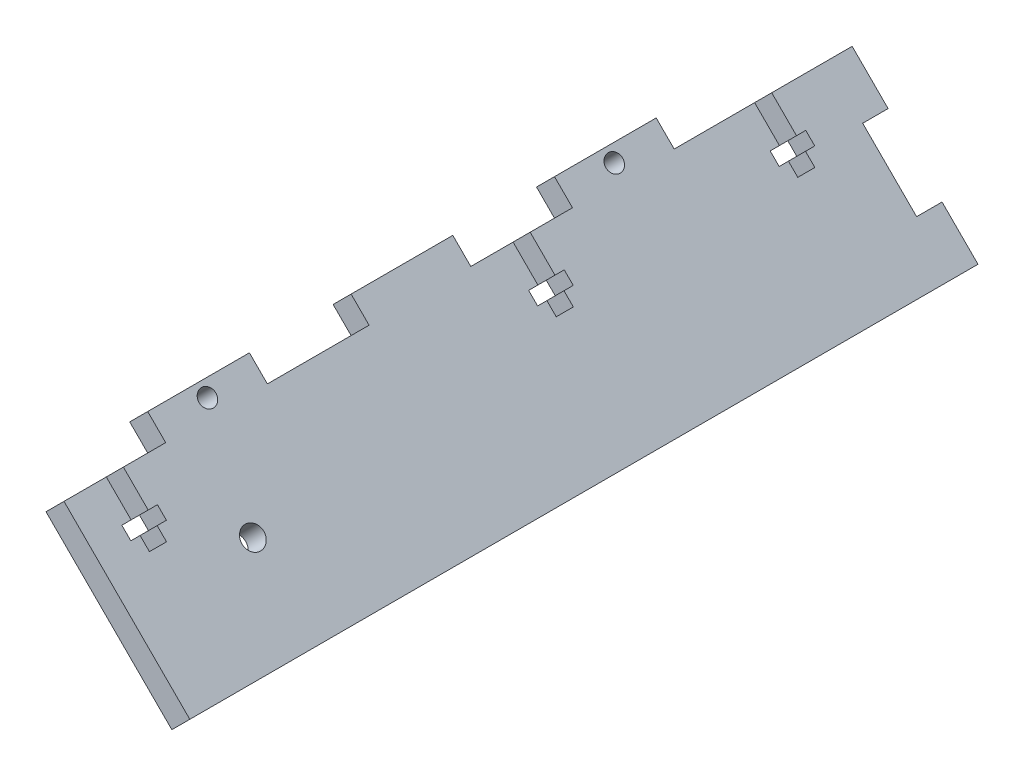
SolidWorks part; units mm, degrees
ref_plane "Front Plane" through (0, 0, 0) normal (0, 0, 1) x (1, 0, 0)
ref_plane "Top Plane" through (0, 0, 0) normal (0, 1, 0) x (1, 0, 0)
ref_plane "Right Plane" through (0, 0, 0) normal (1, 0, 0) x (0, 0, -1)
sketch "Sketch1" plane through (0, 0, 0) normal (0, 0, 1) x (1, 0, 0)
  line L0 (-105.5101, 43.1479) -> (-54.0999, -8.2622) construction
  line L1 (-21.1674, -45.6848) -> (-64.2712, -2.5811) construction
  line L2 (-59.7811, 1.9091) -> (-16.6773, -41.1947) construction
  line L3 (-71.393, 41.3598) -> (-39.9621, 9.9289)
  line L4 (-71.393, 41.3598) -> (-66.9029, 45.85)
  line L5 (-39.9621, 9.9289) -> (-35.472, 14.4191)
  line L6 (-66.9029, 45.85) -> (-35.472, 14.4191)
  line L7 (-72.2911, -22.4) -> (-103.722, 9.0309) construction
  line L8 (-76.7812, -26.8901) -> (-72.2911, -22.4) construction
extrude "Boss-Extrude1" add sketch "Sketch1" along normal up to surface (190.5 mm away)
sketch "Sketch2" plane through (-56.3764, 56.3764, 0) normal (-0.7071, 0.7071, 0) x (0, 0, 1)
  line L0 (190.5, -14.8867) -> (0, -14.8867) construction
  line L1 (165.1, -14.8867) -> (139.7, -14.8867)
  line L2 (165.1, -14.8867) -> (165.1, -21.2367)
  line L3 (165.1, -21.2367) -> (139.7, -21.2367)
  line L4 (139.7, -14.8867) -> (139.7, -21.2367)
  line L5 (190.5, -21.2367) -> (0, -21.2367) construction
  dimension "D1" = 25.4
  dimension "D2" = 25.4
extrude "Boss-Extrude2" add sketch "Sketch2" along normal blind 6.35
pattern_linear "LPattern1" count 3 spacing 50.8 along (0, 0, -1) of "Boss-Extrude2"
sketch "Sketch3" plane through (0, 0, 0) normal (0, 0, -1) x (-1, 0, 0)
  line L0 (71.393, 41.3598) -> (62.4128, 32.3796)
  line L1 (71.393, 41.3598) -> (39.9621, 9.9289) construction
  line L2 (62.4128, 32.3796) -> (57.9227, 36.8697)
  line L3 (35.472, 14.4191) -> (66.9029, 45.85) construction
  line L4 (57.9227, 36.8697) -> (66.9029, 45.85)
  line L5 (66.9029, 45.85) -> (71.393, 41.3598)
  dimension "D1" = 12.7
extrude "Boss-Extrude3" add sketch "Sketch3" along normal blind 6.35
pattern_linear "LPattern2" count 2 spacing 31.75 along (0.7071, -0.7071, 0) of "Boss-Extrude3"
sketch "Sketch4" plane through (-10.5265, -10.5265, 0) normal (0.7071, 0.7071, 0) x (0, 0, -1)
  circle A0 centre (-159.0375, 57.5033) radius 2.7305
extrude "Cut-Extrude1" cut sketch "Sketch4" against normal through all
sketch "Sketch5" plane through (-10.5265, -10.5265, 0) normal (0.7071, 0.7071, 0) x (0, 0, -1)
  line L0 (-177.8, 79.7283) -> (-177.8, 68.4326) construction
  line L1 (-190.5, 79.7283) -> (-165.1, 79.7283) construction
  line L2 (-76.2, 79.7283) -> (-76.2, 62.5112) construction
  line L3 (-88.9, 79.7283) -> (-63.5, 79.7283) construction
  line L4 (-15.875, 79.7283) -> (-15.875, 66.2052) construction
  line L5 (-38.1, 79.7283) -> (6.35, 79.7283) construction
  line L6 (-38.1412, 79.7283) -> (0, 79.7283) construction
  line B0 (-175.6664, 79.7283) -> (-179.9336, 79.7283)
  line B1 (-179.9336, 67.7903) -> (-182.245, 67.7903)
  line B2 (-182.245, 67.7903) -> (-182.245, 70.9653)
  line B3 (-182.245, 70.9653) -> (-179.9336, 70.9653)
  line B4 (-179.9336, 70.9653) -> (-179.9336, 79.7283)
  line B5 (-179.9336, 67.7903) -> (-179.9336, 64.4883)
  line B6 (-179.9336, 64.4883) -> (-175.6664, 64.4883)
  line B7 (-175.6664, 67.7903) -> (-175.6664, 64.4883)
  line B8 (-175.6664, 70.9653) -> (-175.6664, 79.7283)
  line B9 (-173.355, 70.9653) -> (-175.6664, 70.9653)
  line B10 (-173.355, 67.7903) -> (-173.355, 70.9653)
  line B11 (-175.6664, 67.7903) -> (-173.355, 67.7903)
  line B12 (-74.0664, 79.7283) -> (-78.3336, 79.7283)
  line B13 (-78.3336, 67.7903) -> (-80.645, 67.7903)
  line B14 (-80.645, 67.7903) -> (-80.645, 70.9653)
  line B15 (-80.645, 70.9653) -> (-78.3336, 70.9653)
  line B16 (-78.3336, 70.9653) -> (-78.3336, 79.7283)
  line B17 (-78.3336, 67.7903) -> (-78.3336, 64.4883)
  line B18 (-78.3336, 64.4883) -> (-74.0664, 64.4883)
  line B19 (-74.0664, 67.7903) -> (-74.0664, 64.4883)
  line B20 (-74.0664, 70.9653) -> (-74.0664, 79.7283)
  line B21 (-71.755, 70.9653) -> (-74.0664, 70.9653)
  line B22 (-71.755, 67.7903) -> (-71.755, 70.9653)
  line B23 (-74.0664, 67.7903) -> (-71.755, 67.7903)
  line B24 (-13.7414, 79.7283) -> (-18.0086, 79.7283)
  line B25 (-18.0086, 67.7903) -> (-20.32, 67.7903)
  line B26 (-20.32, 67.7903) -> (-20.32, 70.9653)
  line B27 (-20.32, 70.9653) -> (-18.0086, 70.9653)
  line B28 (-18.0086, 70.9653) -> (-18.0086, 79.7283)
  line B29 (-18.0086, 67.7903) -> (-18.0086, 64.4883)
  line B30 (-18.0086, 64.4883) -> (-13.7414, 64.4883)
  line B31 (-13.7414, 67.7903) -> (-13.7414, 64.4883)
  line B32 (-13.7414, 70.9653) -> (-13.7414, 79.7283)
  line B33 (-11.43, 70.9653) -> (-13.7414, 70.9653)
  line B34 (-11.43, 67.7903) -> (-11.43, 70.9653)
  line B35 (-13.7414, 67.7903) -> (-11.43, 67.7903)
sketch_block_instance "TSlot-1"
sketch_block "TSlot" parameters "D1"=3.302, "D2"=3.175
sketch_block_instance "TSlot-2"
sketch_block_instance "TSlot-3"
extrude "Cut-Extrude2" cut sketch "Sketch5" against normal through all
sketch "Sketch6" plane through (-15.0166, -15.0166, 0) normal (-0.7071, -0.7071, 0) x (0, 0, 1)
  line L0 (150.287, 86.0783) -> (154.5542, 79.7283) construction
  line L1 (139.7, 86.0783) -> (165.1, 86.0783) construction
  line L2 (150.287, 86.0783) -> (150.287, 79.7283) construction
  line L3 (154.5542, 86.0783) -> (150.287, 79.7283) construction
  line L4 (154.5542, 79.7283) -> (154.5542, 86.0783) construction
  line L5 (48.687, 86.0783) -> (52.9542, 79.7283) construction
  line L6 (38.1, 86.0783) -> (63.5, 86.0783) construction
  line L7 (48.687, 86.0783) -> (48.687, 79.7283) construction
  line L8 (52.9542, 86.0783) -> (48.687, 79.7283) construction
  line L9 (52.9542, 79.7283) -> (52.9542, 86.0783) construction
  circle A0 centre (152.4206, 82.9033) radius 2.0955
  circle A1 centre (50.8206, 82.9033) radius 2.0955
  dimension "D1" = 4.191
extrude "Cut-Extrude3" cut sketch "Sketch6" against normal through all
